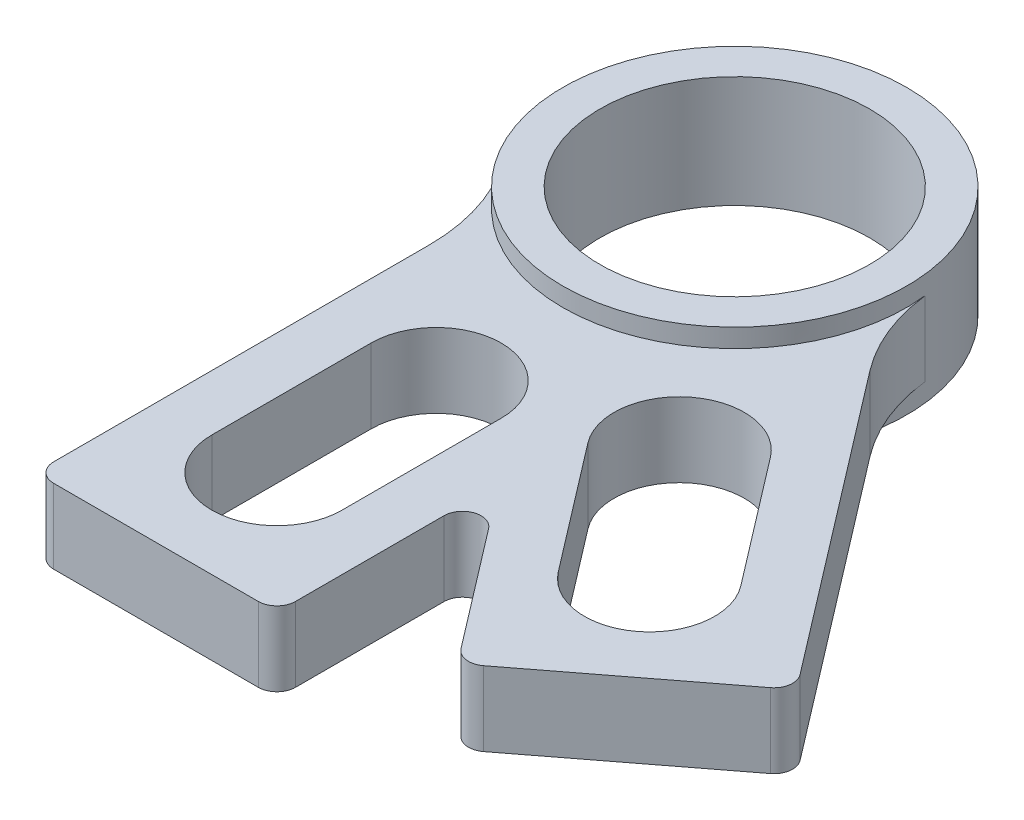
SolidWorks part; units mm, degrees
material "AISI 4130 Steel, annealed at 865C"
ref_plane "Front Plane" through (0, 0, 0) normal (0, 0, 1) x (1, 0, 0)
ref_plane "Top Plane" through (0, 0, 0) normal (0, 1, 0) x (1, 0, 0)
ref_plane "Right Plane" through (0, 0, 0) normal (1, 0, 0) x (0, 0, -1)
sketch "Sketch1" plane through (0, 0, 0) normal (0, 1, 0) x (1, 0, 0)
  line L0 (0, 0) -> (0, -49.3903) construction
  line L1 (0, 0) -> (30.026, -39.2153) construction
  line L2 (0, -39.0716) -> (0, -25.4826) construction
  line L3 (-5.5562, -39.0716) -> (-5.5562, -25.4826)
  line L4 (5.5563, -39.0716) -> (5.5563, -25.4826)
  line L5 (23.7529, -31.0223) -> (15.4917, -20.2328) construction
  line L6 (19.3413, -34.4002) -> (11.0801, -23.6107)
  line L7 (28.1645, -27.6445) -> (19.9033, -16.855)
  line L8 (0, -49.3903) -> (0, -44.6278) construction
  line L9 (30.026, -39.2153) -> (27.1307, -35.4339) construction
  line L10 (-10.3187, -49.3903) -> (10.3188, -49.3903)
  line L11 (21.833, -45.4884) -> (38.219, -32.9422)
  line L12 (-10.3187, -49.3903) -> (-10.3187, -10.4432)
  line L13 (10.3188, -49.3903) -> (10.3188, -30.4502)
  line L14 (38.219, -32.9422) -> (14.5418, -2.0187)
  line L15 (21.833, -45.4884) -> (10.3188, -30.4502)
  line L16 (173.3945, -226.4611) -> (14.2398, -18.5978) construction
  line L22 (0, 0) -> (10.3188, -30.4502) construction
  circle A0 centre (0, 0) radius 11.5062
  circle A1 centre (0, 0) radius 14.6812
  arc A2 (-5.5562, -39.0716) -> (5.5563, -39.0716) centre (0, -39.0716) ccw
  arc A3 (5.5563, -25.4826) -> (-5.5562, -25.4826) centre (0, -25.4826) ccw
  arc A4 (19.3413, -34.4002) -> (28.1645, -27.6445) centre (23.7529, -31.0223) ccw
  arc A5 (19.9033, -16.855) -> (11.0801, -23.6107) centre (15.4917, -20.2328) ccw
  point P8 (0, -32.2771)
  point P13 (19.6223, -25.6276)
  point P25 (0, -49.3903)
  point P27 (30.026, -39.2153)
  dimension "D2" = 29.3624
  dimension "D3" = 4.7625
  dimension "D4" = 4.7625
  dimension "D5" = 13.589
  dimension "D6" = 49.3903
  dimension "D7" = 20.6375
extrude "Bearing_Insert_Extrude" add sketch "Sketch1" along normal mid plane 9.525 contours A1 A0 region at (-5.4988, 0, -13.1636)
extrude "Apex_Slot_Insert_Extrude" add sketch "Sketch1<4>" along normal mid plane 6.35 contours A1 L12 L10 L13 L15 L11 L14 A5 L7 A4 L6 A3 L4 A2 L3 region at (9.7498, 0, 28.7713)
sketch "Sketch1<4>" plane through (0, 0, 0) normal (0, 1, 0) x (1, 0, 0) same geometry as "Sketch1"
fillet "Fillet1" radius 16.002 2 edges at (14.5418, 0, 2.0187) (-10.3187, 0, 10.4432)
fillet "Fillet2" radius 1.5875 5 edges at (38.219, 0, 32.9422) (21.833, 0, 45.4884) (10.3188, 0, 30.4502) (10.3188, 0, 49.3903) (-10.3187, 0, 49.3903)
equation "\"Apex_thickness\"= .25"
equation "\"Bearing_diameter\"= 0.906in"
equation "\"A-arm_angle\"= 39.1893"
equation "\"D1@Sketch1\"=\"Bearing_diameter\""
equation "\"D1@Apex_Slot_Insert_Extrude\"=\"Apex_thickness\""
